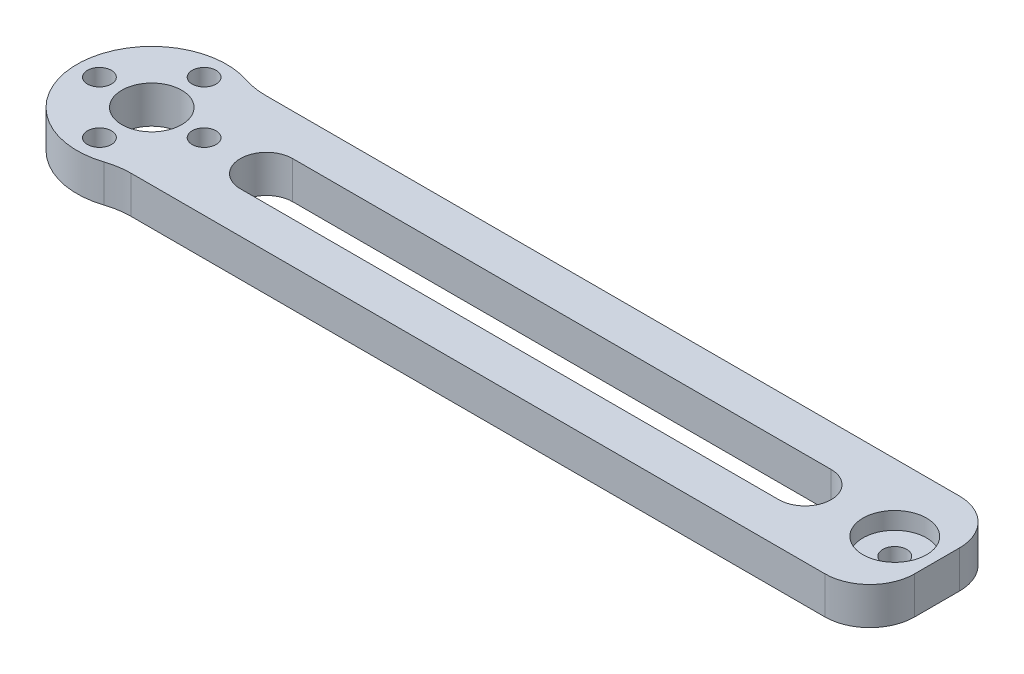
SolidWorks part; units mm, degrees
ref_plane "前视基准面" through (0, 0, 0) normal (0, 0, 1) x (1, 0, 0)
ref_plane "上视基准面" through (0, 0, 0) normal (0, 1, 0) x (1, 0, 0)
ref_plane "右视基准面" through (0, 0, 0) normal (1, 0, 0) x (0, 0, -1)
other "Configuration Table"
sketch "草图1" plane through (0, 0, 0) normal (0, 1, 0) x (1, 0, 0)
  line L0 (0, 0) -> (-9, 0) construction
  line L1 (0, 9) -> (99, 9)
  line L2 (105, 3) -> (105, -3)
  line L3 (99, -9) -> (0, -9)
  line L4 (0, 0) -> (99.34, 0) construction
  line L5 (15.34, 0) -> (87.34, 0) construction
  line L6 (15.34, 3.5) -> (87.34, 3.5)
  line L7 (15.34, -3.5) -> (87.34, -3.5)
  circle A0 centre (0, 0) radius 4
  circle A1 centre (0, 0) radius 9
  circle A2 centre (0, 0) radius 7 construction
  circle A4 centre (-7, 0) radius 1.6
  circle A5 centre (0, 7) radius 1.6
  circle A6 centre (7, 0) radius 1.6
  circle A7 centre (0, -7) radius 1.6
  circle A8 centre (99.34, 0) radius 1.6
  arc A9 (15.34, 3.5) -> (15.34, -3.5) centre (15.34, 0) ccw
  arc A10 (87.34, -3.5) -> (87.34, 3.5) centre (87.34, 0) ccw
  arc A11 (105, -3) -> (99, -9) centre (99, -3) cw
  arc A12 (99, 9) -> (105, 3) centre (99, 3) cw
  point P17 (0, 0)
  point P23 (51.34, 0)
  point P32 (105, 9)
  dimension "D1" = 18
  dimension "D2" = 8
  dimension "D3" = 14
  dimension "D4" = 3.2
  dimension "D7" = 3.2
  dimension "D12" = 3.5
  dimension "D13" = 6
  dimension "D6" = 105
  dimension "D8" = 9
  dimension "D9" = 5.66
  dimension "D10" = 72
  dimension "D11" = 12
  dimension "D5" = 4
extrude "凸台-拉伸1" add sketch "草图1" along normal blind 5 contours A12 L1 A1 L3 A11 L2 A10 L7 A9 L6 A8 | A1 A7 A6 A5 A4 A0 region at (49.5, 0, -7.9347) region at (6.184, 0, -6.184)
sketch "草图2" plane through (0, 5, 0) normal (0, 1, 0) x (1, 0, 0)
  circle A0 centre (99.34, 0) radius 4.25
  dimension "D1" = 8.5
extrude "切除-拉伸1" cut sketch "草图2" against normal blind 2.3
sketch "草图3" plane through (0, 5, 0) normal (0, 1, 0) x (1, 0, 0)
  circle A0 centre (0, 0) radius 10
  circle A1 centre (0, 0) radius 9
  dimension "D1" = 18
  dimension "D2" = 20
extrude "凸台-拉伸2" add sketch "草图3" against normal blind 5
fillet "圆角1" radius 10 2 edges at (4.3589, 2.5, 9) (4.3589, 2.5, -9)
